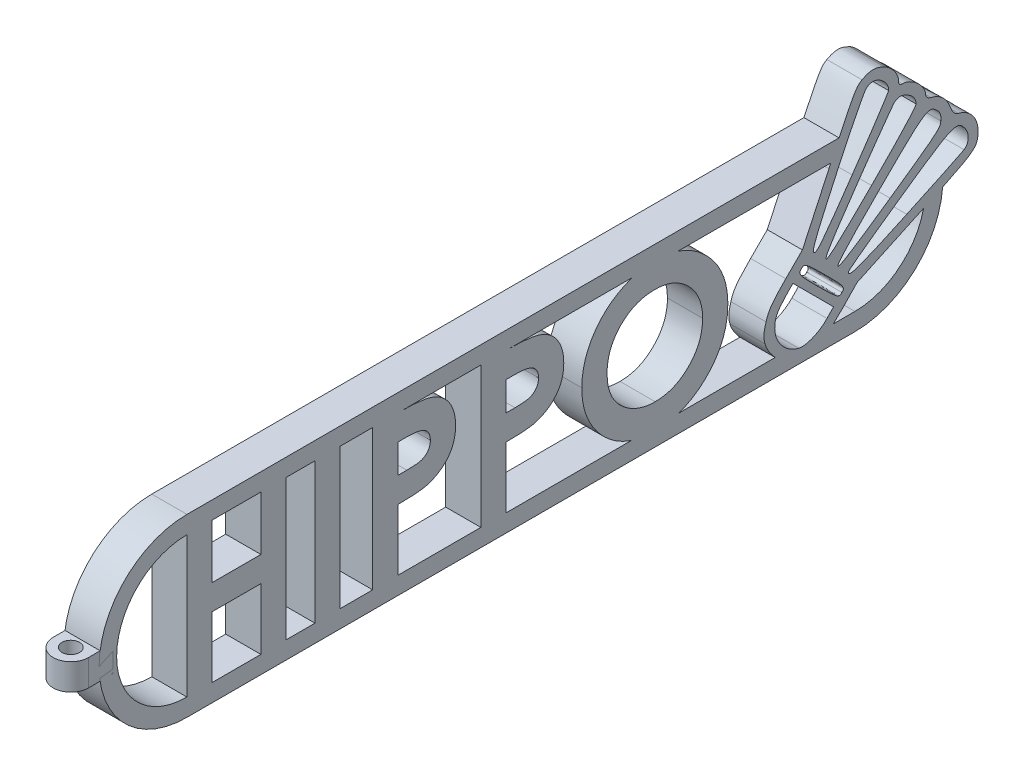
SolidWorks part; units mm, degrees
ref_plane "Front Plane" through (0, 0, 0) normal (0, 0, 1) x (1, 0, 0)
ref_plane "Top Plane" through (0, 0, 0) normal (0, 1, 0) x (1, 0, 0)
ref_plane "Right Plane" through (0, 0, 0) normal (1, 0, 0) x (0, 0, -1)
sketch "Sketch1" plane through (0, 0, 0) normal (1, 0, 0) x (0, 0, -1)
  text T0 "<b>HIPPO</b>" font "Century Gothic" height 16
extrude "Boss-Extrude1" add sketch "Sketch1" along normal blind 3
sketch "Sketch2" plane through (3, 0, 0) normal (1, 0, 0) x (0, 0, -1)
  line L0 (1.8462, 0) -> (1.8462, 16) construction
  line L1 (1.8462, -2) -> (84.1318, -2)
  line L2 (74.8872, 15.5422) -> (71.8699, 9.0451)
  line L3 (71.8699, 9.0451) -> (69.9759, 7.1511)
  line L4 (76.4068, 0.9844) -> (78.0807, 2.7243)
  line L5 (78.0807, 2.7243) -> (84.6438, 5.7856)
  line L6 (69.9979, 5.4772) -> (70.7907, 6.2921)
  line L7 (70.7907, 6.2921) -> (73.1032, 3.9796)
  line L8 (73.1032, 3.9796) -> (75.4158, 1.6671)
  line L9 (75.4158, 1.6671) -> (74.6669, 0.8963)
  line L10 (1.8462, 8) -> (77.8462, 8)
  line L11 (1.8462, 18) -> (77.8462, 18)
  line L12 (1.8462, 16) -> (77.8462, 16)
  line L13 (1.8462, 0) -> (77.8462, 0)
  circle A0 centre (1.8462, 8) radius 8
  circle A1 centre (1.8462, 8) radius 10
  circle A2 centre (77.8462, 8) radius 10
  circle A3 centre (77.8462, 8) radius 8
  spline S0 degree 3 poles (78.6533, 22.4136) (77.9705, 22.0833) (77.6402, 21.4446) (74.8872, 15.5422) knots 0 0 0 0 1 1 1 1
  spline S1 degree 3 poles (69.9759, 7.1511) (68.3681, 5.5213) (68.0377, 5.0588) (67.7294, 4.0237) knots 0 0 0 0 1 1 1 1
  spline S2 degree 3 poles (67.7294, 4.0237) (67.4431, 3.0326) (67.4211, 2.6141) (67.6193, 1.8873) knots 0 0 0 0 1 1 1 1
  spline S3 degree 3 poles (67.6193, 1.8873) (67.9056, 0.8082) (69.1389, -0.6234) (70.2842, -1.218) knots 0 0 0 0 1 1 1 1
  spline S4 degree 3 poles (70.2842, -1.218) (72.2003, -2.1871) (73.9842, -1.5264) (76.4068, 0.9844) knots 0 0 0 0 1 1 1 1
  spline S5 degree 3 poles (84.6438, 5.7856) (91.7795, 9.0671) (91.8456, 9.1332) (91.8456, 10.8511) knots 0 0 0 0 1 1 1 1
  spline S6 degree 3 poles (91.8456, 10.8511) (91.8456, 12.1505) (90.9206, 13.3178) (89.6212, 13.6261) knots 0 0 0 0 1 1 1 1
  spline S7 degree 3 poles (89.6212, 13.6261) (89.2027, 13.7362) (88.9384, 14.0225) (88.6742, 14.7713) knots 0 0 0 0 1 1 1 1
  spline S8 degree 3 poles (88.6742, 14.7713) (88.2777, 15.8065) (87.5069, 16.5112) (86.4938, 16.7535) knots 0 0 0 0 1 1 1 1
  spline S9 degree 3 poles (86.4938, 16.7535) (86.1414, 16.8416) (85.8991, 17.0618) (85.8991, 17.2821) knots 0 0 0 0 1 1 1 1
  spline S10 degree 3 poles (85.8991, 17.2821) (85.8991, 18.2952) (84.3575, 19.7267) (83.2563, 19.7267) knots 0 0 0 0 1 1 1 1
  spline S11 degree 3 poles (83.2563, 19.7267) (82.9479, 19.7267) (82.8158, 19.8589) (82.8158, 20.1892) knots 0 0 0 0 1 1 1 1
  spline S12 degree 3 poles (82.8158, 20.1892) (82.8158, 20.938) (82.089, 21.9511) (81.2301, 22.3916) knots 0 0 0 0 1 1 1 1
  spline S13 degree 3 poles (81.2301, 22.3916) (80.217, 22.9202) (79.6223, 22.9202) (78.6533, 22.4136) knots 0 0 0 0 1 1 1 1
  spline S14 degree 3 poles (81.2301, 20.894) (81.5384, 20.5416) (81.7146, 20.1231) (81.6706, 19.8589) knots 0 0 0 0 1 1 1 1
  spline S15 degree 3 poles (81.6706, 19.8589) (81.6045, 19.5946) (79.7545, 16.7975) (77.5301, 13.6041) knots 0 0 0 0 1 1 1 1
  spline S16 degree 3 poles (77.5301, 13.6041) (74.0723, 8.6267) (73.4556, 7.8558) (73.1913, 8.1201) knots 0 0 0 0 1 1 1 1
  spline S17 degree 3 poles (73.1913, 8.1201) (72.9271, 8.3844) (73.2794, 9.3094) (75.7681, 14.6832) knots 0 0 0 0 1 1 1 1
  spline S18 degree 3 poles (75.7681, 14.6832) (77.3539, 18.119) (78.8735, 21.1142) (79.1378, 21.3345) knots 0 0 0 0 1 1 1 1
  spline S19 degree 3 poles (79.1378, 21.3345) (79.7324, 21.841) (80.5473, 21.6648) (81.2301, 20.894) knots 0 0 0 0 1 1 1 1
  spline S20 degree 3 poles (83.7628, 18.3612) (84.4015, 18.0309) (84.7759, 17.5243) (84.7979, 16.9737) knots 0 0 0 0 1 1 1 1
  spline S21 degree 3 poles (84.7979, 16.9737) (84.7979, 16.6874) (83.036, 14.7713) (79.7324, 11.4677) knots 0 0 0 0 1 1 1 1
  spline S22 degree 3 poles (79.7324, 11.4677) (73.2134, 4.9707) (72.9931, 5.1249) (78.2128, 12.613) knots 0 0 0 0 1 1 1 1
  spline S23 degree 3 poles (78.2128, 12.613) (80.3051, 15.6082) (82.1551, 18.2071) (82.3533, 18.3612) knots 0 0 0 0 1 1 1 1
  spline S24 degree 3 poles (82.3533, 18.3612) (82.7717, 18.6916) (83.1462, 18.6916) (83.7628, 18.3612) knots 0 0 0 0 1 1 1 1
  spline S25 degree 3 poles (87.2426, 15.0797) (87.5509, 14.7713) (87.6611, 14.419) (87.617, 13.8904) knots 0 0 0 0 1 1 1 1
  spline S26 degree 3 poles (87.617, 13.8904) (87.5509, 13.1856) (87.2206, 12.9213) (81.8467, 9.1552) knots 0 0 0 0 1 1 1 1
  spline S27 degree 3 poles (81.8467, 9.1552) (77.7943, 6.3142) (76.0765, 5.235) (75.9003, 5.4112) knots 0 0 0 0 1 1 1 1
  spline S28 degree 3 poles (75.9003, 5.4112) (75.7461, 5.5653) (77.0896, 7.063) (80.6134, 10.5868) knots 0 0 0 0 1 1 1 1
  spline S29 degree 3 poles (80.6134, 10.5868) (85.9212, 15.8946) (86.2295, 16.0928) (87.2426, 15.0797) knots 0 0 0 0 1 1 1 1
  spline S30 degree 3 poles (90.2819, 11.8862) (90.8986, 11.0933) (90.8766, 10.1463) (90.2599, 9.7279) knots 0 0 0 0 1 1 1 1
  spline S31 degree 3 poles (90.2599, 9.7279) (89.9736, 9.5517) (87.0444, 8.1421) (83.7408, 6.6225) knots 0 0 0 0 1 1 1 1
  spline S32 degree 3 poles (83.7408, 6.6225) (78.3009, 4.0897) (76.8914, 3.6052) (77.1336, 4.31) knots 0 0 0 0 1 1 1 1
  spline S33 degree 3 poles (77.1336, 4.31) (77.1777, 4.4421) (79.7324, 6.3142) (82.8158, 8.4725) knots 0 0 0 0 1 1 1 1
  spline S34 degree 3 poles (82.8158, 8.4725) (88.9384, 12.7672) (89.423, 12.9874) (90.2819, 11.8862) knots 0 0 0 0 1 1 1 1
  spline S35 degree 3 poles (76.3628, 2.6141) (76.0104, 2.2397) (75.8783, 2.3498) (73.6759, 4.5302) knots 0 0 0 0 1 1 1 1
  spline S36 degree 3 poles (73.6759, 4.5302) (71.4955, 6.7106) (71.3854, 6.8427) (71.7378, 7.2392) knots 0 0 0 0 1 1 1 1
  spline S37 degree 3 poles (71.7378, 7.2392) (72.0901, 7.6136) (72.2003, 7.5255) (74.4247, 5.3231) knots 0 0 0 0 1 1 1 1
  spline S38 degree 3 poles (74.4247, 5.3231) (76.6271, 3.1207) (76.7372, 2.9665) (76.3628, 2.6141) knots 0 0 0 0 1 1 1 1
  spline S39 degree 3 poles (74.6669, 0.8963) (73.764, -0.0508) (72.2884, -0.6454) (71.4294, -0.4252) knots 0 0 0 0 1 1 1 1
  spline S40 degree 3 poles (71.4294, -0.4252) (69.9318, -0.0728) (68.7205, 1.4248) (68.7205, 2.8784) knots 0 0 0 0 1 1 1 1
  spline S41 degree 3 poles (68.7205, 2.8784) (68.7205, 3.8695) (68.9848, 4.3981) (69.9979, 5.4772) knots 0 0 0 0 1 1 1 1
  point P69 (0, 0)
  line M5 (1.8462, 0) -> (4.7179, 0)
  line M9 (10.2564, 0) -> (13.1282, 0)
  line M11 (13.1282, 16) -> (10.2564, 16)
  line M15 (4.7179, 16) -> (1.8462, 16)
  dimension "D2" = 2
  dimension "D1" = 2
extrude "Boss-Extrude2" add sketch "Sketch2" against normal blind 3 contours A2 S34 S30 S31 S5 S6 S7 S8 S9 S10 S11 S12 S13 S0 L11 S18 S19 S14 S15 S23 S24 S20 S21 S29 S25 S26 | A3 S23 A2 S15 | L12 S18 A2 S0 | A3 S18 L12 S0 L2 | S22 S23 A3 S15 S16 S17 S18 L2 L3 L10 | A2 S18 L11 S0 | A3 S29 A2 S21 | L9 S39 A3 S4 L4 L5 S5 S31 S32 S33 S34 S26 S27 S28 S29 S21 S22 L10 L3 S1 L6 L7 L8 S37 S38 S35 S36 | A3 S34 A2 S26 | A2 S31 A3 S5 | S5 A3 L13 S4 A2 | L13 S39 A2 S4 | A3 S39 L13 S4 | S39 S40 L13 S3 S4 A2 | S40 S41 A2 S1 S2 S3 L13 | A2 S41 L6 A3 S1 | S0 A2 L12 | S0 L11 A1 L12 A2 M11 | S4 S3 L13 A1 L1 A2 M9 | L12 A1 L13 A0 M5 M15 region at (3, -1.033, -38.6325) region at (3, 8, 7.8977) region at (3, -1.6179, -75.8061) region at (3, 17.0225, -39.8175) region at (3, -0.8404, -71.2672) region at (3, -0.4458, -73.8685) region at (3, 7.4077, -86.8029) region at (3, 16.1247, -84.8789) region at (3, 17.9452, -76.4366) region at (3, 0.2603, -74.6585) region at (3, 6.211, -85.0591) region at (3, 16.6879, -74.2086) region at (3, 16.9636, -76.2066) region at (3, 2.153, -68.4649) region at (3, 15.8059, -75.5124) region at (3, 5.4531, -69.219) region at (3, 11.4875, -86.1504) region at (3, 16.6454, -80.3292) region at (3, 8.4352, -71.4347) region at (3, 14.7142, -83.8581)
ref_plane "Plane1" through (0, 8, 0) normal (0, -1, 0) x (-1, 0, 0)
sketch "Sketch4" plane through (3, 0, 0) normal (1, 0, 0) x (0, 0, -1)
  line L1 (1.8462, 0) -> (1.8462, 16)
  line L2 (1.8462, 0) -> (1.8462, 16)
  line L4 (1.8462, -2) -> (77.8462, -2)
  line L5 (75.3816, 0) -> (77.8462, 0)
  line L6 (78.0807, 2.7243) -> (76.4068, 0.9844)
  line L7 (84.6438, 5.7856) -> (78.0807, 2.7243)
  line L8 (75.3816, 0) -> (77.8462, 0)
  line L9 (78.0807, 2.7243) -> (76.4068, 0.9844)
  line L10 (84.6438, 5.7856) -> (78.0807, 2.7243)
  line L11 (70.7907, 6.2921) -> (69.9979, 5.4772)
  line L12 (75.4158, 1.6671) -> (70.7907, 6.2921)
  line L13 (74.6669, 0.8963) -> (75.4158, 1.6671)
  line L14 (70.7907, 6.2921) -> (69.9979, 5.4772)
  line L15 (75.4158, 1.6671) -> (70.7907, 6.2921)
  line L16 (74.6669, 0.8963) -> (75.4158, 1.6671)
  line L17 (25.8462, 9.8462) -> (26.8622, 9.8462)
  line L18 (10.2564, 0) -> (10.2564, 6.9744)
  line L19 (4.7179, 0) -> (10.2564, 0)
  line L20 (4.7179, 6.9744) -> (4.7179, 0)
  line L21 (10.2564, 6.9744) -> (4.7179, 6.9744)
  line L22 (10.2564, 0) -> (10.2564, 6.9744)
  line L23 (4.7179, 0) -> (10.2564, 0)
  line L24 (4.7179, 6.9744) -> (4.7179, 0)
  line L25 (10.2564, 6.9744) -> (4.7179, 6.9744)
  line L26 (4.7179, 16) -> (4.7179, 9.8462)
  line L27 (10.2564, 16) -> (4.7179, 16)
  line L28 (10.2564, 9.8462) -> (10.2564, 16)
  line L29 (4.7179, 9.8462) -> (10.2564, 9.8462)
  line L30 (4.7179, 16) -> (4.7179, 9.8462)
  line L31 (10.2564, 16) -> (4.7179, 16)
  line L32 (10.2564, 9.8462) -> (10.2564, 16)
  line L33 (4.7179, 9.8462) -> (10.2564, 9.8462)
  line L34 (13.1282, 16) -> (13.1282, 0)
  line L35 (16.4103, 16) -> (13.1282, 16)
  line L36 (16.4103, 0) -> (16.4103, 16)
  line L37 (13.1282, 0) -> (16.4103, 0)
  line L38 (13.1282, 16) -> (13.1282, 0)
  line L39 (16.4103, 16) -> (13.1282, 16)
  line L40 (16.4103, 0) -> (16.4103, 16)
  line L41 (13.1282, 0) -> (16.4103, 0)
  line L42 (19.2821, 16) -> (19.2821, 0)
  line L43 (22.9744, 16) -> (19.2821, 16)
  line L44 (22.9744, 0) -> (22.9744, 16)
  line L45 (19.2821, 0) -> (22.9744, 0)
  line L46 (19.2821, 16) -> (19.2821, 0)
  line L47 (22.9744, 16) -> (19.2821, 16)
  line L48 (22.9744, 0) -> (22.9744, 16)
  line L49 (19.2821, 0) -> (22.9744, 0)
  line L50 (25.8462, 13.1282) -> (25.8462, 9.8462)
  line L51 (26.75, 13.1282) -> (25.8462, 13.1282)
  line L52 (25.8462, 9.8462) -> (26.8622, 9.8462)
  line L53 (25.8462, 13.1282) -> (25.8462, 9.8462)
  line L54 (26.75, 13.1282) -> (25.8462, 13.1282)
  line L55 (38.1538, 9.8462) -> (39.1699, 9.8462)
  line L56 (35.2821, 16) -> (26.1795, 16)
  line L57 (35.2821, 0) -> (35.2821, 16)
  line L58 (25.8462, 0) -> (35.2821, 0)
  line L59 (25.8462, 6.9744) -> (25.8462, 0)
  line L60 (35.2821, 16) -> (26.1795, 16)
  line L61 (35.2821, 0) -> (35.2821, 16)
  line L62 (25.8462, 0) -> (35.2821, 0)
  line L63 (25.8462, 6.9744) -> (25.8462, 0)
  line L64 (38.1538, 13.1282) -> (38.1538, 9.8462)
  line L65 (39.0577, 13.1282) -> (38.1538, 13.1282)
  line L66 (38.1538, 9.8462) -> (39.1699, 9.8462)
  line L67 (38.1538, 13.1282) -> (38.1538, 9.8462)
  line L68 (39.0577, 13.1282) -> (38.1538, 13.1282)
  line L69 (38.1538, 0) -> (52.4084, 0)
  line L70 (57.788, 0) -> (68.765, 0)
  line L71 (75.1008, 16) -> (57.7211, 16)
  line L72 (71.8699, 9.0451) -> (74.8872, 15.5422)
  line L73 (69.9759, 7.1511) -> (71.8699, 9.0451)
  line L74 (57.788, 0) -> (68.765, 0)
  line L75 (75.1008, 16) -> (57.7211, 16)
  line L76 (71.8699, 9.0451) -> (74.8872, 15.5422)
  line L77 (69.9759, 7.1511) -> (71.8699, 9.0451)
  line L78 (38.1538, 6.9744) -> (38.1538, 0)
  line L79 (52.5121, 16) -> (38.4872, 16)
  line L80 (38.1538, 0) -> (52.4084, 0)
  line L81 (38.1538, 6.9744) -> (38.1538, 0)
  line L82 (52.5121, 16) -> (38.4872, 16)
  line L83 (76.038, 18) -> (1.8462, 18)
  line L84 (1.8462, -2) -> (77.8462, -2)
  line L85 (76.038, 18) -> (1.8462, 18)
  arc A1 (1.8462, 16) -> (1.8462, 0) centre (1.8462, 8) ccw
  arc A2 (1.8462, 16) -> (1.8462, 0) centre (1.8462, 8) ccw
  arc A3 (77.8462, 0) -> (85.6524, 6.2499) centre (77.8462, 8) ccw
  arc A4 (77.8462, 0) -> (85.6524, 6.2499) centre (77.8462, 8) ccw
  arc A5 (75.1008, 16) -> (74.8872, 15.5422) centre (1612.4659, -701.5915) ccw
  arc A6 (75.1008, 16) -> (74.8872, 15.5422) centre (1612.4659, -701.5915) ccw
  arc A8 (1.8462, 18) -> (1.8462, -2) centre (1.8462, 8) ccw
  arc A9 (77.8462, -2) -> (87.8186, 7.2582) centre (77.8462, 8) ccw
  arc A10 (1.8462, 18) -> (1.8462, -2) centre (1.8462, 8) ccw
  arc A11 (77.8462, -2) -> (87.8186, 7.2582) centre (77.8462, 8) ccw
  spline S2 degree 3 poles (3398.8035, 2205.2477) (-3328.0157, -1472.5897) (3668.6024, 610.8811) (-3872.9047, 380.9278) knots -14.449432 -14.449432 -14.449432 -14.449432 18.771452 18.771452 18.771452 18.771452 only from (76.4068, 0.9844) to (75.3816, 0)
  spline S3 degree 3 poles (3203.2755, 2509.8402) (-3117.551, -2311.6664) (3402.2738, 2198.6029) (-3322.7745, -2087.971) knots -8.590322 -8.590322 -8.590322 -8.590322 6.910663 6.910663 6.910663 6.910663 only from (85.6524, 6.2499) to (84.6438, 5.7856)
  spline S4 degree 3 poles (76.4068, 0.9844) (76.0522, 0.6168) (75.7112, 0.2889) (75.3816, 0) knots 0.853614 0.853614 0.853614 0.853614 1 1 1 1
  spline S5 degree 3 poles (85.6524, 6.2499) (85.3329, 6.1026) (84.997, 5.948) (84.6438, 5.7856) knots 0 0 0 0 0.049503 0.049503 0.049503 0.049503
  spline S7 degree 3 poles (3662.2888, 1757.5012) (-3665.795, -1581.4606) (3896.598, 1366.2039) (-3765.3568, -1110.8259) knots -14.001225 -14.001225 -14.001225 -14.001225 15.36382 15.36382 15.36382 15.36382 only from (71.4294, -0.4252) to (74.6669, 0.8963)
  spline S8 degree 3 poles (3245.6319, -2431.8344) (-3158.4345, 2357.2343) (3374.3152, -2236.2437) (-3319.5499, 2126.5847) knots -10.133548 -10.133548 -10.133548 -10.133548 12.175041 12.175041 12.175041 12.175041 only from (74.4247, 5.3231) to (71.7378, 7.2392)
  spline S9 degree 3 poles (1083.5594, 3850.6057) (607.2877, -1937.4836) (-1991.6838, 100.7189) (3666.0332, 1714.9301) knots -11.026375 -11.026375 -11.026375 -11.026375 11.921239 11.921239 11.921239 11.921239 only from (78.2128, 12.613) to (79.7324, 11.4677)
  spline S10 degree 3 poles (1641.4402, 3695.284) (-1451.7816, -3694.7067) (1537.8192, 3732.2131) (-1312.2249, -3743.7308) knots -8.732068 -8.732068 -8.732068 -8.732068 11.138373 11.138373 11.138373 11.138373 only from (75.7681, 14.6832) to (73.1913, 8.1201)
  spline S11 degree 3 poles (-1691.1806, -3565.3513) (1950.1636, 3740.9223) (-1835.9314, -3700.9685) (1948.2953, 3549.0256) knots -10.471686 -10.471686 -10.471686 -10.471686 12.804548 12.804548 12.804548 12.804548 only from (79.1378, 21.3345) to (75.7681, 14.6832)
  spline S12 degree 3 poles (-3902.9668, 52.302) (3987.908, -662.1434) (-3687.842, 1284.6522) (3652.9871, -1753.1124) knots -22.160522 -22.160522 -22.160522 -22.160522 22.114231 22.114231 22.114231 22.114231 only from (81.2301, 20.894) to (79.1378, 21.3345)
  spline S13 degree 3 poles (-1660.4023, 3619.2004) (1672.625, -3686.2371) (-1329.5129, 3799.7603) (1281.2887, -3793.0689) knots -24.742089 -24.742089 -24.742089 -24.742089 26.636419 26.636419 26.636419 26.636419 only from (81.6706, 19.8589) to (81.2301, 20.894)
  spline S14 degree 3 poles (2243.6041, 3376.228) (-2219.7676, -3488.6997) (2391.2134, 3493.9099) (-2149.5274, -3299.8374) knots -11.951522 -11.951522 -11.951522 -11.951522 11.519907 11.519907 11.519907 11.519907 only from (77.5301, 13.6041) to (81.6706, 19.8589)
  spline S15 degree 3 poles (-2493.0411, -3059.458) (2574.1796, 3146.3373) (-2373.0325, -3175.9895) (2473.7465, 3216.155) knots -10.235719 -10.235719 -10.235719 -10.235719 9.730338 9.730338 9.730338 9.730338 only from (73.1913, 8.1201) to (77.5301, 13.6041)
  spline S16 degree 3 poles (75.7681, 14.6832) (73.2794, 9.3094) (72.9271, 8.3844) (73.1913, 8.1201) knots 0 0 0 0 1 1 1 1
  spline S17 degree 3 poles (79.1378, 21.3345) (78.8735, 21.1142) (77.3539, 18.119) (75.7681, 14.6832) knots 0 0 0 0 1 1 1 1
  spline S18 degree 3 poles (81.2301, 20.894) (80.5473, 21.6648) (79.7324, 21.841) (79.1378, 21.3345) knots 0 0 0 0 1 1 1 1
  spline S19 degree 3 poles (81.6706, 19.8589) (81.7146, 20.1231) (81.5384, 20.5416) (81.2301, 20.894) knots 0 0 0 0 1 1 1 1
  spline S20 degree 3 poles (77.5301, 13.6041) (79.7545, 16.7975) (81.6045, 19.5946) (81.6706, 19.8589) knots 0 0 0 0 1 1 1 1
  spline S21 degree 3 poles (73.1913, 8.1201) (73.4556, 7.8558) (74.0723, 8.6267) (77.5301, 13.6041) knots 0 0 0 0 1 1 1 1
  spline S22 degree 3 poles (-2176.0719, -3282.7953) (2439.0711, 3449.1497) (-2293.0545, -3426.5564) (2353.9475, 3301.8808) knots -10.65011 -10.65011 -10.65011 -10.65011 13.034154 13.034154 13.034154 13.034154 only from (82.3533, 18.3612) to (78.2128, 12.613)
  spline S23 degree 3 poles (4041.3379, -533.1759) (-3834.4966, 213.1099) (3997.2825, 202.3854) (-3869.2711, -565.3494) knots -23.09562 -23.09562 -23.09562 -23.09562 24.773781 24.773781 24.773781 24.773781 only from (83.7628, 18.3612) to (82.3533, 18.3612)
  spline S24 degree 3 poles (-2738.2129, 2838.4609) (2525.552, -3137.8393) (-1904.1707, 3471.2601) (1544.442, -3691.9755) knots -28.231758 -28.231758 -28.231758 -28.231758 30.196206 30.196206 30.196206 30.196206 only from (84.7979, 16.9737) to (83.7628, 18.3612)
  spline S25 degree 3 poles (2219.6275, 3340.4099) (-3988.2905, -4500.1893) (3827.8531, 3873.0493) (-2752.2579, -2802.2224) knots -31.935784 -31.935784 -31.935784 -31.935784 18.597569 18.597569 18.597569 18.597569 only from (79.7324, 11.4677) to (84.7979, 16.9737)
  spline S26 degree 3 poles (78.2128, 12.613) (72.9931, 5.1249) (73.2134, 4.9707) (79.7324, 11.4677) knots 0 0 0 0 1 1 1 1
  spline S27 degree 3 poles (82.3533, 18.3612) (82.1551, 18.2071) (80.3051, 15.6082) (78.2128, 12.613) knots 0 0 0 0 1 1 1 1
  spline S28 degree 3 poles (83.7628, 18.3612) (83.1462, 18.6916) (82.7717, 18.6916) (82.3533, 18.3612) knots 0 0 0 0 1 1 1 1
  spline S29 degree 3 poles (84.7979, 16.9737) (84.7759, 17.5243) (84.4015, 18.0309) (83.7628, 18.3612) knots 0 0 0 0 1 1 1 1
  spline S30 degree 3 poles (79.7324, 11.4677) (83.036, 14.7713) (84.7979, 16.6874) (84.7979, 16.9737) knots 0 0 0 0 1 1 1 1
  spline S31 degree 3 poles (-3066.9036, -2457.2821) (3189.1374, 2517.7206) (-2963.5188, -2546.6324) (3090.9577, 2654.8825) knots -7.650295 -7.650295 -7.650295 -7.650295 9.619482 9.619482 9.619482 9.619482 only from (81.8467, 9.1552) to (87.617, 13.8904)
  spline S32 degree 3 poles (-3420.4834, -1932.3599) (3708.7133, 2282.0815) (-3460.812, -2345.5677) (3380.3356, 2271.2505) knots -18.576445 -18.576445 -18.576445 -18.576445 14.352502 14.352502 14.352502 14.352502 only from (75.9003, 5.4112) to (81.8467, 9.1552)
  spline S33 degree 3 poles (2949.1906, 2798.1479) (-2957.8136, -2975.5538) (3103.5037, 3054.5658) (-2663.5684, -2908.2041) knots -13.235152 -13.235152 -13.235152 -13.235152 19.430166 19.430166 19.430166 19.430166 only from (80.6134, 10.5868) to (75.9003, 5.4112)
  spline S34 degree 3 poles (3560.9209, 1993.6135) (-3246.9405, -2160.7019) (3316.2473, 2353.498) (-3070.6661, -2451.6) knots -8.33373 -8.33373 -8.33373 -8.33373 8.314581 8.314581 8.314581 8.314581 only from (87.2426, 15.0797) to (80.6134, 10.5868)
  spline S35 degree 3 poles (818.7962, -3914.4503) (-968.034, 3784.8593) (1496.8532, -3635.1385) (-1706.2685, 3584.7352) knots -29.576927 -29.576927 -29.576927 -29.576927 31.263424 31.263424 31.263424 31.263424 only from (87.617, 13.8904) to (87.2426, 15.0797)
  spline S36 degree 3 poles (81.8467, 9.1552) (87.2206, 12.9213) (87.5509, 13.1856) (87.617, 13.8904) knots 0 0 0 0 1 1 1 1
  spline S37 degree 3 poles (75.9003, 5.4112) (76.0765, 5.235) (77.7943, 6.3142) (81.8467, 9.1552) knots 0 0 0 0 1 1 1 1
  spline S38 degree 3 poles (80.6134, 10.5868) (77.0896, 7.063) (75.7461, 5.5653) (75.9003, 5.4112) knots 0 0 0 0 1 1 1 1
  spline S39 degree 3 poles (87.2426, 15.0797) (86.2295, 16.0928) (85.9212, 15.8946) (80.6134, 10.5868) knots 0 0 0 0 1 1 1 1
  spline S40 degree 3 poles (87.617, 13.8904) (87.6611, 14.419) (87.5509, 14.7713) (87.2426, 15.0797) knots 0 0 0 0 1 1 1 1
  spline S41 degree 3 poles (3653.7082, 1810.546) (-3652.9096, -1852.2843) (3822.3539, 1845.7708) (-3504.7072, -1743.7789) knots -11.926091 -11.926091 -11.926091 -11.926091 11.61226 11.61226 11.61226 11.61226 only from (83.7408, 6.6225) to (90.2599, 9.7279)
  spline S42 degree 3 poles (-3769.4158, -1084.4312) (3943.5137, 1339.5694) (-3734.9681, -1469.0708) (3780.149, 1534.2354) knots -12.484067 -12.484067 -12.484067 -12.484067 10.943657 10.943657 10.943657 10.943657 only from (77.1336, 4.31) to (83.7408, 6.6225)
  spline S43 degree 3 poles (-3119.3021, -2388.2991) (3453.2703, 2492.5539) (-3293.1517, -2451.1802) (3320.394, 2345.0708) knots -12.142018 -12.142018 -12.142018 -12.142018 11.645217 11.645217 11.645217 11.645217 only from (82.8158, 8.4725) to (77.1336, 4.31)
  spline S44 degree 3 poles (3848.8812, 1373.4178) (-3562.3293, -1567.477) (3667.0055, 1769.2314) (-3440.104, -1884.3095) knots -8.472057 -8.472057 -8.472057 -8.472057 8.419331 8.419331 8.419331 8.419331 only from (90.2819, 11.8862) to (82.8158, 8.4725)
  spline S45 degree 3 poles (-247.3283, 3990.3134) (41.0963, -3999.1804) (545.8079, 3993.3576) (-788.1207, -3883.4417) knots -17.288999 -17.288999 -17.288999 -17.288999 18.710016 18.710016 18.710016 18.710016 only from (90.2599, 9.7279) to (90.2819, 11.8862)
  spline S46 degree 3 poles (83.7408, 6.6225) (87.0444, 8.1421) (89.9736, 9.5517) (90.2599, 9.7279) knots 0 0 0 0 1 1 1 1
  spline S47 degree 3 poles (77.1336, 4.31) (76.8914, 3.6052) (78.3009, 4.0897) (83.7408, 6.6225) knots 0 0 0 0 1 1 1 1
  spline S48 degree 3 poles (82.8158, 8.4725) (79.7324, 6.3142) (77.1777, 4.4421) (77.1336, 4.31) knots 0 0 0 0 1 1 1 1
  spline S49 degree 3 poles (90.2819, 11.8862) (89.423, 12.9874) (88.9384, 12.7672) (82.8158, 8.4725) knots 0 0 0 0 1 1 1 1
  spline S50 degree 3 poles (90.2599, 9.7279) (90.8766, 10.1463) (90.8986, 11.0933) (90.2819, 11.8862) knots 0 0 0 0 1 1 1 1
  spline S51 degree 3 poles (2226.2291, -3369.2735) (-2199.2504, 3283.3199) (2458.9196, -3203.9324) (-2394.7214, 3151.668) knots -11.348512 -11.348512 -11.348512 -11.348512 11.266484 11.266484 11.266484 11.266484 only from (76.3628, 2.6141) to (74.4247, 5.3231)
  spline S52 degree 3 poles (-3108.0054, 2427.9194) (3318.4109, -2330.2254) (-3239.8458, 2224.9499) (3483.4831, -2090.8877) knots -10.243964 -10.243964 -10.243964 -10.243964 12.306567 12.306567 12.306567 12.306567 only from (73.6759, 4.5302) to (76.3628, 2.6141)
  spline S53 degree 3 poles (-2027.9667, 3410.5578) (2298.8876, -3302.9973) (-2266.395, 3242.6264) (2504.5121, -3171.3971) knots -11.246626 -11.246626 -11.246626 -11.246626 11.218548 11.218548 11.218548 11.218548 only from (71.7378, 7.2392) to (73.6759, 4.5302)
  spline S54 degree 3 poles (74.4247, 5.3231) (72.2003, 7.5255) (72.0901, 7.6136) (71.7378, 7.2392) knots 0 0 0 0 1 1 1 1
  spline S55 degree 3 poles (76.3628, 2.6141) (76.7372, 2.9665) (76.6271, 3.1207) (74.4247, 5.3231) knots 0 0 0 0 1 1 1 1
  spline S56 degree 3 poles (73.6759, 4.5302) (75.8783, 2.3498) (76.0104, 2.2397) (76.3628, 2.6141) knots 0 0 0 0 1 1 1 1
  spline S57 degree 3 poles (71.7378, 7.2392) (71.3854, 6.8427) (71.4955, 6.7106) (73.6759, 4.5302) knots 0 0 0 0 1 1 1 1
  spline S58 degree 3 poles (2920.3551, -2795.4819) (-2554.5373, 3081.8895) (2411.2536, -3299.6806) (-1934.0115, 3454.9016) knots -13.355319 -13.355319 -13.355319 -13.355319 14.387707 14.387707 14.387707 14.387707 only from (68.7205, 2.8784) to (71.4294, -0.4252)
  spline S59 degree 3 poles (2056.7145, 3475.7087) (-1724.927, -3505.3927) (1679.2284, 3599.0436) (-1369.3069, -3727.8202) knots -14.481772 -14.481772 -14.481772 -14.481772 15.937559 15.937559 15.937559 15.937559 only from (69.9979, 5.4772) to (68.7205, 2.8784)
  spline S60 degree 3 poles (71.4294, -0.4252) (72.2884, -0.6454) (73.764, -0.0508) (74.6669, 0.8963) knots 0 0 0 0 1 1 1 1
  spline S61 degree 3 poles (68.7205, 2.8784) (68.7205, 1.4248) (69.9318, -0.0728) (71.4294, -0.4252) knots 0 0 0 0 1 1 1 1
  spline S62 degree 3 poles (69.9979, 5.4772) (68.9848, 4.3981) (68.7205, 3.8695) (68.7205, 2.8784) knots 0 0 0 0 1 1 1 1
  spline S63 degree 3 poles (1654.4282, 3667.4926) (23.5895, -27.9887) (34.1837, 10.9726) (28.4438, 12.9542) (28.2324, 13.0075) (27.9915, 13.0518) (27.7218, 13.0862) (27.4235, 13.1124) (8.673, 13.7177) (-10.0794, -12.057) (-13.112, 4012.472) knots -8.463627 -8.463627 -8.463627 -8.463627 0.082101 0.173825 0.278953 0.396639 0.527316 0.671298 0.828754 27.604848 27.604848 27.604848 27.604848 only from (28.7853, 12.8109) to (26.75, 13.1282)
  spline S64 degree 3 poles (4016.0561, 337.084) (-13.681, -5.9368) (30.6901, 4.9208) (29.495, 11.8885) (29.4377, 12.0841) (29.3546, 12.2635) (29.2471, 12.4263) (29.1161, 12.5724) (24.4224, 16.6446) (-8.0727, -19.3212) (2299.6561, 3305.3954) knots -12.573831 -12.573831 -12.573831 -12.573831 0.137788 0.267341 0.390444 0.511778 0.629509 0.747829 0.871885 12.00493 12.00493 12.00493 12.00493 only from (29.5385, 11.4583) to (28.7853, 12.8109)
  spline S65 degree 3 poles (82.6352, -3989.4601) (-6.2739, 55.6737) (11.3504, 8.7728) (27.8518, 9.8807) (28.2252, 9.9283) (28.5201, 9.9966) (28.753, 10.1003) (28.9538, 10.2203) (29.1261, 10.3719) (29.2753, 10.5452) (29.3945, 10.7444) (29.4772, 10.9661) (31.0003, 17.7613) (-21.0415, 30.2799) (4007.9526, -399.2926) knots -13.479945 -13.479945 -13.479945 -13.479945 0.15516 0.285496 0.390503 0.470975 0.538446 0.603655 0.666587 0.730199 0.794945 0.860228 0.928121 6.609006 6.609006 6.609006 6.609006 only from (26.8622, 9.8462) to (29.5385, 11.4583)
  spline S66 degree 3 poles (28.7853, 12.8109) (28.7345, 12.8366) (28.6269, 12.891) (28.4438, 12.9542) (28.2324, 13.0075) (27.9915, 13.0518) (27.7218, 13.0862) (27.4235, 13.1124) (27.0962, 13.123) (26.8686, 13.1264) (26.75, 13.1282) knots 0 0 0 0 0.082101 0.173825 0.278953 0.396639 0.527316 0.671298 0.828754 1 1 1 1
  spline S67 degree 3 poles (29.5385, 11.4583) (29.5359, 11.5333) (29.531, 11.6787) (29.495, 11.8885) (29.4377, 12.0841) (29.3546, 12.2635) (29.2471, 12.4263) (29.1161, 12.5724) (28.9632, 12.705) (28.8452, 12.7752) (28.7853, 12.8109) knots 0 0 0 0 0.137788 0.267341 0.390444 0.511778 0.629509 0.747829 0.871885 1 1 1 1
  spline S68 degree 3 poles (26.8622, 9.8462) (27.0471, 9.8473) (27.3872, 9.8495) (27.8518, 9.8807) (28.2252, 9.9283) (28.5201, 9.9966) (28.753, 10.1003) (28.9538, 10.2203) (29.1261, 10.3719) (29.2753, 10.5452) (29.3945, 10.7444) (29.4772, 10.9661) (29.5309, 11.2058) (29.5359, 11.3726) (29.5385, 11.4583) knots 0 0 0 0 0.15516 0.285496 0.390503 0.470975 0.538446 0.603655 0.666587 0.730199 0.794945 0.860228 0.928121 1 1 1 1
  spline S69 degree 3 poles (18.4847, 4015.3868) (-17.5505, -22.4135) (5.1105, 16.8134) (27.3755, 15.9753) (27.913, 15.936) (28.4053, 15.8875) (28.8521, 15.8194) (29.254, 15.7413) (29.6111, 15.6462) (29.9274, 15.5333) (30.2113, 15.4002) (30.4799, 15.2585) (30.7273, 15.0893) (30.9658, 14.911) (31.1818, 14.7064) (31.3889, 14.4892) (31.5782, 14.2508) (31.7506, 13.994) (31.9071, 13.7236) (32.0437, 13.4392) (32.1546, 13.1402) (32.2476, 12.8286) (32.3223, 12.5045) (32.372, 12.1657) (33.4736, 0.718) (-10.6404, -12.802) (4028.728, 171.1984) knots -7.331892 -7.331892 -7.331892 -7.331892 0.070781 0.136552 0.197012 0.252923 0.303687 0.349719 0.39124 0.428479 0.463057 0.49715 0.531002 0.564226 0.597701 0.631421 0.665597 0.700451 0.735881 0.771092 0.806975 0.843534 0.88094 0.919294 0.95918 4.764652 4.764652 4.764652 4.764652 only from (26.1795, 16) to (32.4103, 11.4551)
  spline S70 degree 3 poles (865.0881, -3903.9323) (38.1814, 49.2581) (37.5026, 8.4748) (28.552, 7.1085) (28.2132, 7.0672) (27.8285, 7.0317) (27.3976, 7.0076) (26.9211, 6.9888) (4.1279, 6.3916) (-18.9183, 40.8656) (6.0459, -3992.438) knots -8.01137 -8.01137 -8.01137 -8.01137 0.077373 0.167614 0.272108 0.390016 0.521363 0.667272 0.82681 21.401594 21.401594 21.401594 21.401594 only from (29.1058, 7.2179) to (25.8462, 6.9744)
  spline S71 degree 3 poles (4029.0232, -146.2279) (-13.6725, 36.5479) (33.6527, 22.504) (32.3618, 10.6739) (32.29, 10.3068) (32.1962, 9.9546) (32.0654, 9.623) (31.916, 9.3042) (31.7322, 9.007) (31.5221, 8.7277) (31.2927, 8.4642) (31.0385, 8.2239) (30.7643, 8.0053) (30.4718, 7.806) (30.1598, 7.6265) (29.8286, 7.4651) (18.7502, 3.1245) (-6.916, 43.6405) (1243.1047, -3803.8094) knots -5.924554 -5.924554 -5.924554 -5.924554 0.068875 0.135349 0.199289 0.26155 0.322915 0.382772 0.442844 0.502652 0.562749 0.62274 0.682687 0.743329 0.805013 0.868067 0.933111 6.929396 6.929396 6.929396 6.929396 only from (32.4103, 11.4551) to (29.1058, 7.2179)
  spline S72 degree 3 poles (26.1795, 16) (26.3889, 15.9991) (26.7929, 15.9973) (27.3755, 15.9753) (27.913, 15.936) (28.4053, 15.8875) (28.8521, 15.8194) (29.254, 15.7413) (29.6111, 15.6462) (29.9274, 15.5333) (30.2113, 15.4002) (30.4799, 15.2585) (30.7273, 15.0893) (30.9658, 14.911) (31.1818, 14.7064) (31.3889, 14.4892) (31.5782, 14.2508) (31.7506, 13.994) (31.9071, 13.7236) (32.0437, 13.4392) (32.1546, 13.1402) (32.2476, 12.8286) (32.3223, 12.5045) (32.372, 12.1657) (32.4058, 11.8148) (32.4087, 11.5759) (32.4103, 11.4551) knots 0 0 0 0 0.070781 0.136552 0.197012 0.252923 0.303687 0.349719 0.39124 0.428479 0.463057 0.49715 0.531002 0.564226 0.597701 0.631421 0.665597 0.700451 0.735881 0.771092 0.806975 0.843534 0.88094 0.919294 0.95918 1 1 1 1
  spline S73 degree 3 poles (29.1058, 7.2179) (29.0237, 7.1975) (28.8461, 7.1533) (28.552, 7.1085) (28.2132, 7.0672) (27.8285, 7.0317) (27.3976, 7.0076) (26.9211, 6.9888) (26.3986, 6.9751) (26.0353, 6.9746) (25.8462, 6.9744) knots 0 0 0 0 0.077373 0.167614 0.272108 0.390016 0.521363 0.667272 0.82681 1 1 1 1
  spline S74 degree 3 poles (32.4103, 11.4551) (32.4081, 11.3215) (32.4038, 11.0588) (32.3618, 10.6739) (32.29, 10.3068) (32.1962, 9.9546) (32.0654, 9.623) (31.916, 9.3042) (31.7322, 9.007) (31.5221, 8.7277) (31.2927, 8.4642) (31.0385, 8.2239) (30.7643, 8.0053) (30.4718, 7.806) (30.1598, 7.6265) (29.8286, 7.4651) (29.4759, 7.3269) (29.2303, 7.2546) (29.1058, 7.2179) knots 0 0 0 0 0.068875 0.135349 0.199289 0.26155 0.322915 0.382772 0.442844 0.502652 0.562749 0.62274 0.682687 0.743329 0.805013 0.868067 0.933111 1 1 1 1
  spline S75 degree 3 poles (1666.7359, 3667.4926) (35.8971, -27.9887) (46.4914, 10.9726) (40.7515, 12.9542) (40.5401, 13.0075) (40.2991, 13.0518) (40.0295, 13.0862) (39.7312, 13.1124) (20.9807, 13.7177) (2.2283, -12.057) (-0.8043, 4012.472) knots -8.463627 -8.463627 -8.463627 -8.463627 0.082101 0.173825 0.278953 0.396639 0.527316 0.671298 0.828754 27.604848 27.604848 27.604848 27.604848 only from (41.0929, 12.8109) to (39.0577, 13.1282)
  spline S76 degree 3 poles (4028.3638, 337.084) (-1.3733, -5.9368) (42.9978, 4.9208) (41.8027, 11.8885) (41.7454, 12.0841) (41.6623, 12.2635) (41.5548, 12.4263) (41.4238, 12.5724) (36.7301, 16.6446) (4.235, -19.3212) (2311.9638, 3305.3954) knots -12.573831 -12.573831 -12.573831 -12.573831 0.137788 0.267341 0.390444 0.511778 0.629509 0.747829 0.871885 12.00493 12.00493 12.00493 12.00493 only from (41.8462, 11.4583) to (41.0929, 12.8109)
  spline S77 degree 3 poles (94.9429, -3989.4601) (6.0338, 55.6737) (23.6581, 8.7728) (40.1595, 9.8807) (40.5329, 9.9283) (40.8278, 9.9966) (41.0607, 10.1003) (41.2615, 10.2203) (41.4338, 10.3719) (41.583, 10.5452) (41.7022, 10.7444) (41.7849, 10.9661) (43.308, 17.7613) (-8.7338, 30.2799) (4020.2603, -399.2926) knots -13.479945 -13.479945 -13.479945 -13.479945 0.15516 0.285496 0.390503 0.470975 0.538446 0.603655 0.666587 0.730199 0.794945 0.860228 0.928121 6.609006 6.609006 6.609006 6.609006 only from (39.1699, 9.8462) to (41.8462, 11.4583)
  spline S78 degree 3 poles (41.0929, 12.8109) (41.0422, 12.8366) (40.9346, 12.891) (40.7515, 12.9542) (40.5401, 13.0075) (40.2991, 13.0518) (40.0295, 13.0862) (39.7312, 13.1124) (39.4039, 13.123) (39.1763, 13.1264) (39.0577, 13.1282) knots 0 0 0 0 0.082101 0.173825 0.278953 0.396639 0.527316 0.671298 0.828754 1 1 1 1
  spline S79 degree 3 poles (41.8462, 11.4583) (41.8436, 11.5333) (41.8387, 11.6787) (41.8027, 11.8885) (41.7454, 12.0841) (41.6623, 12.2635) (41.5548, 12.4263) (41.4238, 12.5724) (41.2709, 12.705) (41.1529, 12.7752) (41.0929, 12.8109) knots 0 0 0 0 0.137788 0.267341 0.390444 0.511778 0.629509 0.747829 0.871885 1 1 1 1
  spline S80 degree 3 poles (39.1699, 9.8462) (39.3548, 9.8473) (39.6949, 9.8495) (40.1595, 9.8807) (40.5329, 9.9283) (40.8278, 9.9966) (41.0607, 10.1003) (41.2615, 10.2203) (41.4338, 10.3719) (41.583, 10.5452) (41.7022, 10.7444) (41.7849, 10.9661) (41.8386, 11.2058) (41.8436, 11.3726) (41.8462, 11.4583) knots 0 0 0 0 0.15516 0.285496 0.390503 0.470975 0.538446 0.603655 0.666587 0.730199 0.794945 0.860228 0.928121 1 1 1 1
  spline S83 degree 3 poles (4057.3795, -202.3989) (0.8783, 47.9515) (65.8196, 25.0106) (63.2485, 6.2701) (63.0583, 5.4741) (62.7962, 4.7103) (62.4526, 3.9825) (62.0386, 3.2861) (61.5432, 2.6275) (60.9846, 2.0071) (60.3696, 1.444) (59.7182, 0.9477) (59.0334, 0.5272) (25.5681, -15.5531) (-112.5681, 218.9867) (3617.3834, 1801.5724) knots -4.136185 -4.136185 -4.136185 -4.136185 0.065722 0.129508 0.191722 0.253161 0.314316 0.375952 0.43862 0.502973 0.567129 0.629552 0.690477 0.751072 9.12812 9.12812 9.12812 9.12812 only from (63.3846, 7.9519) to (57.788, 0)
  spline S84 degree 3 poles (3946.9638, 936.8697) (-101.0334, -183.9215) (27.7375, 30.7571) (58.9881, 15.4576) (59.6761, 15.0339) (60.3327, 14.5296) (60.9511, 13.9563) (61.5225, 13.3329) (62.0177, 12.6617) (62.44, 11.9601) (62.7899, 11.2262) (63.0565, 10.455) (63.2436, 9.6503) (65.8886, -8.791) (-0.9472, -31.9394) (4056.0087, 240.8891) knots -7.551136 -7.551136 -7.551136 -7.551136 0.245977 0.306108 0.367351 0.429902 0.49454 0.559373 0.62241 0.684357 0.745807 0.80743 0.869996 0.933928 5.045645 5.045645 5.045645 5.045645 only from (57.7211, 16) to (63.3846, 7.9519)
  spline S85 degree 3 poles (-2135.0973, -3334.1205) (2339.4421, 3239.3435) (-2290.3901, -3168.8056) (2531.4661, 3159.4805) knots -12.058741 -12.058741 -12.058741 -12.058741 12.483005 12.483005 12.483005 12.483005 only from (67.7294, 4.0237) to (69.9759, 7.1511)
  spline S86 degree 3 poles (63.8036, -3997.3468) (202.2048, 3955.5937) (-195.2913, -3944.4981) (455.4203, 3984.4741) knots -16.166508 -16.166508 -16.166508 -16.166508 16.841536 16.841536 16.841536 16.841536 only from (67.6193, 1.8873) to (67.7294, 4.0237)
  spline S87 degree 3 poles (-2343.6217, 3188.918) (2673.6749, -3129.7678) (-2672.2732, 3010.203) (2889.9913, -2830.7166) knots -13.7139 -13.7139 -13.7139 -13.7139 13.676704 13.676704 13.676704 13.676704 only from (68.765, 0) to (67.6193, 1.8873)
  spline S88 degree 3 poles (63.3846, 7.9519) (63.3771, 7.6652) (63.3624, 7.1003) (63.2485, 6.2701) (63.0583, 5.4741) (62.7962, 4.7103) (62.4526, 3.9825) (62.0386, 3.2861) (61.5432, 2.6275) (60.9846, 2.0071) (60.3696, 1.444) (59.7182, 0.9477) (59.0334, 0.5272) (58.3869, 0.2165) (57.9646, 0.0587) (57.788, 0) knots 0 0 0 0 0.065722 0.129508 0.191722 0.253161 0.314316 0.375952 0.43862 0.502973 0.567129 0.629552 0.690477 0.751072 0.793733 0.793733 0.793733 0.793733
  spline S89 degree 3 poles (57.7211, 16) (57.9053, 15.9387) (58.3345, 15.7776) (58.9881, 15.4576) (59.6761, 15.0339) (60.3327, 14.5296) (60.9511, 13.9563) (61.5225, 13.3329) (62.0177, 12.6617) (62.44, 11.9601) (62.7899, 11.2262) (63.0565, 10.455) (63.2436, 9.6503) (63.3638, 8.8124) (63.3776, 8.2419) (63.3846, 7.9519) knots 0.20174 0.20174 0.20174 0.20174 0.245977 0.306108 0.367351 0.429902 0.49454 0.559373 0.62241 0.684357 0.745807 0.80743 0.869996 0.933928 1 1 1 1
  spline S90 degree 3 poles (67.7294, 4.0237) (68.0377, 5.0588) (68.3681, 5.5213) (69.9759, 7.1511) knots 0 0 0 0 1 1 1 1
  spline S91 degree 3 poles (67.6193, 1.8873) (67.4211, 2.6141) (67.4431, 3.0326) (67.7294, 4.0237) knots 0 0 0 0 1 1 1 1
  spline S92 degree 3 poles (68.765, 0) (68.2133, 0.6053) (67.7755, 1.2987) (67.6193, 1.8873) knots 0 0 0 0 0.545427 0.545427 0.545427 0.545427
  spline S93 degree 3 poles (-186.4192, 4005.8683) (85.8422, -40.9619) (67.9321, 15.3945) (53.9654, 13.448) (53.4451, 13.3274) (52.9494, 13.1526) (52.476, 12.9302) (52.0242, 12.6609) (51.6002, 12.3355) (51.1983, 11.9714) (50.8353, 11.5658) (50.5146, 11.131) (50.2462, 10.6679) (50.0214, 10.1808) (49.8522, 9.6641) (49.7317, 9.122) (47.7745, -5.4879) (104.803, -23.8592) (-3943.6503, 232.664) knots -4.669718 -4.669718 -4.669718 -4.669718 0.064609 0.127512 0.188521 0.248708 0.308598 0.368812 0.429888 0.492802 0.555743 0.617485 0.678969 0.740198 0.80236 0.866245 0.931707 5.881016 5.881016 5.881016 5.881016 only from (55.0641, 13.5385) to (49.641, 7.9679)
  spline S94 degree 3 poles (4053.9812, 230.0537) (6.211, -23.0775) (62.3581, -5.159) (60.4231, 9.1065) (60.2976, 9.6344) (60.1239, 10.1401) (59.902, 10.6242) (59.6277, 11.0848) (59.3019, 11.5216) (58.932, 11.9316) (58.5294, 12.3084) (58.0972, 12.6354) (57.6475, 12.9195) (57.1698, 13.1421) (56.6742, 13.3194) (56.1574, 13.45) (42.0203, 15.3622) (24.4656, -39.9898) (264.6187, 4007.7101) knots -4.783709 -4.783709 -4.783709 -4.783709 0.065939 0.129791 0.192175 0.253617 0.314719 0.376282 0.438973 0.503175 0.567329 0.629651 0.69065 0.751238 0.811754 0.872788 0.93554 5.741199 5.741199 5.741199 5.741199 only from (60.5128, 7.9904) to (55.0641, 13.5385)
  spline S95 degree 3 poles (284.5506, -3990.6765) (24.8855, 56.7367) (42.4149, 0.6177) (56.1997, 2.5512) (56.7092, 2.6774) (57.1996, 2.8506) (57.6695, 3.0758) (58.1164, 3.3535) (58.5413, 3.6801) (58.9426, 4.049) (59.3095, 4.4562) (59.6295, 4.8933) (59.9064, 5.3505) (60.1265, 5.8344) (60.3024, 6.3404) (60.4215, 6.8706) (62.3843, 20.986) (5.311, 39.1662) (4052.5899, -238.0371) knots -4.65552 -4.65552 -4.65552 -4.65552 0.064147 0.126212 0.186841 0.246936 0.307256 0.368151 0.430071 0.493875 0.557981 0.62087 0.682525 0.744036 0.805889 0.868968 0.933247 5.766235 5.766235 5.766235 5.766235 only from (55.1218, 2.4615) to (60.5128, 7.9904)
  spline S96 degree 3 poles (-2278.4661, -3247.2748) (61.0289, 60.8655) (41.184, 10.0353) (52.3986, 3.1497) (52.8171, 2.9359) (53.2508, 2.7631) (53.6989, 2.6272) (54.1613, 2.532) (67.2359, 0.8914) (83.5376, 53.0977) (-157.8266, -3991.5384) knots -10.005791 -10.005791 -10.005791 -10.005791 0.127991 0.253098 0.376184 0.498936 0.621526 0.745707 0.871575 11.016998 11.016998 11.016998 11.016998 only from (51.609, 3.6923) to (55.1218, 2.4615)
  spline S97 degree 3 poles (-3943.0203, -226.9682) (107.2391, 41.7858) (47.5375, 22.1696) (49.7499, 6.6918) (49.9032, 6.0997) (50.1246, 5.5453) (50.3993, 5.0225) (50.7403, 4.5378) (60.1113, -5.9467) (114.0632, 31.1195) (-2663.3034, -2933.3522) knots -9.200931 -9.200931 -9.200931 -9.200931 0.134807 0.264199 0.388462 0.509942 0.63041 0.750671 0.873455 9.247787 9.247787 9.247787 9.247787 only from (49.641, 7.9679) to (51.609, 3.6923)
  spline S98 degree 3 poles (55.0641, 13.5385) (54.8769, 13.5334) (54.5074, 13.5235) (53.9654, 13.448) (53.4451, 13.3274) (52.9494, 13.1526) (52.476, 12.9302) (52.0242, 12.6609) (51.6002, 12.3355) (51.1983, 11.9714) (50.8353, 11.5658) (50.5146, 11.131) (50.2462, 10.6679) (50.0214, 10.1808) (49.8522, 9.6641) (49.7317, 9.122) (49.6555, 8.5534) (49.6459, 8.1658) (49.641, 7.9679) knots 0 0 0 0 0.064609 0.127512 0.188521 0.248708 0.308598 0.368812 0.429888 0.492802 0.555743 0.617485 0.678969 0.740198 0.80236 0.866245 0.931707 1 1 1 1
  spline S99 degree 3 poles (60.5128, 7.9904) (60.5078, 8.1808) (60.4978, 8.5556) (60.4231, 9.1065) (60.2976, 9.6344) (60.1239, 10.1401) (59.902, 10.6242) (59.6277, 11.0848) (59.3019, 11.5216) (58.932, 11.9316) (58.5294, 12.3084) (58.0972, 12.6354) (57.6475, 12.9195) (57.1698, 13.1421) (56.6742, 13.3194) (56.1574, 13.45) (55.6175, 13.523) (55.2502, 13.5333) (55.0641, 13.5385) knots 0 0 0 0 0.065939 0.129791 0.192175 0.253617 0.314719 0.376282 0.438973 0.503175 0.567329 0.629651 0.69065 0.751238 0.811754 0.872788 0.93554 1 1 1 1
  spline S100 degree 3 poles (55.1218, 2.4615) (55.3058, 2.4666) (55.6678, 2.4766) (56.1997, 2.5512) (56.7092, 2.6774) (57.1996, 2.8506) (57.6695, 3.0758) (58.1164, 3.3535) (58.5413, 3.6801) (58.9426, 4.049) (59.3095, 4.4562) (59.6295, 4.8933) (59.9064, 5.3505) (60.1265, 5.8344) (60.3024, 6.3404) (60.4215, 6.8706) (60.4983, 7.423) (60.5079, 7.7989) (60.5128, 7.9904) knots 0 0 0 0 0.064147 0.126212 0.186841 0.246936 0.307256 0.368151 0.430071 0.493875 0.557981 0.62087 0.682525 0.744036 0.805889 0.868968 0.933247 1 1 1 1
  spline S101 degree 3 poles (51.609, 3.6923) (51.7377, 3.5939) (51.9923, 3.3992) (52.3986, 3.1497) (52.8171, 2.9359) (53.2508, 2.7631) (53.6989, 2.6272) (54.1613, 2.532) (54.6373, 2.4723) (54.9592, 2.4651) (55.1218, 2.4615) knots 0 0 0 0 0.127991 0.253098 0.376184 0.498936 0.621526 0.745707 0.871575 1 1 1 1
  spline S102 degree 3 poles (49.641, 7.9679) (49.6475, 7.7486) (49.6603, 7.3188) (49.7499, 6.6918) (49.9032, 6.0997) (50.1246, 5.5453) (50.3993, 5.0225) (50.7403, 4.5378) (51.1422, 4.0881) (51.4518, 3.8256) (51.609, 3.6923) knots 0 0 0 0 0.134807 0.264199 0.388462 0.509942 0.63041 0.750671 0.873455 1 1 1 1
  spline S103 degree 3 poles (-227.9973, 3988.0639) (151.4258, 96.6419) (75.8363, -11.2496) (51.0996, 0.5521) (50.4055, 0.9834) (49.7514, 1.495) (49.1412, 2.074) (48.5883, 2.7074) (48.1003, 3.3766) (47.6886, 4.0765) (47.3533, 4.8072) (47.089, 5.5644) (46.9025, 6.3526) (44.3781, 25.0841) (108.0335, 47.9424) (-3947.1531, -203.028) knots -5.833008 -5.833008 -5.833008 -5.833008 0.255326 0.316388 0.378027 0.440406 0.504557 0.568658 0.630986 0.692288 0.752615 0.8132 0.874016 0.936158 5.09426 5.09426 5.09426 5.09426 only from (52.4084, 0) to (46.7692, 8.0064)
  spline S104 degree 3 poles (877.3958, -3903.9323) (50.4891, 49.2581) (49.8102, 8.4748) (40.8597, 7.1085) (40.5209, 7.0672) (40.1362, 7.0317) (39.7053, 7.0076) (39.2288, 6.9888) (16.4356, 6.3916) (-6.6106, 40.8656) (18.3536, -3992.438) knots -8.01137 -8.01137 -8.01137 -8.01137 0.077373 0.167614 0.272108 0.390016 0.521363 0.667272 0.82681 21.401594 21.401594 21.401594 21.401594 only from (41.4135, 7.2179) to (38.1538, 6.9744)
  spline S105 degree 3 poles (4041.3309, -146.2279) (-1.3648, 36.5479) (45.9604, 22.504) (44.6695, 10.6739) (44.5977, 10.3068) (44.5039, 9.9546) (44.3731, 9.623) (44.2237, 9.3042) (44.0399, 9.007) (43.8298, 8.7277) (43.6004, 8.4642) (43.3462, 8.2239) (43.072, 8.0053) (42.7795, 7.806) (42.4675, 7.6265) (42.1363, 7.4651) (31.0579, 3.1245) (5.3917, 43.6405) (1255.4123, -3803.8094) knots -5.924554 -5.924554 -5.924554 -5.924554 0.068875 0.135349 0.199289 0.26155 0.322915 0.382772 0.442844 0.502652 0.562749 0.62274 0.682687 0.743329 0.805013 0.868067 0.933111 6.929396 6.929396 6.929396 6.929396 only from (44.7179, 11.4551) to (41.4135, 7.2179)
  spline S106 degree 3 poles (30.7924, 4015.3868) (-5.2428, -22.4135) (17.4182, 16.8134) (39.6832, 15.9753) (40.2207, 15.936) (40.713, 15.8875) (41.1598, 15.8194) (41.5617, 15.7413) (41.9188, 15.6462) (42.2351, 15.5333) (42.519, 15.4002) (42.7876, 15.2585) (43.035, 15.0893) (43.2735, 14.911) (43.4895, 14.7064) (43.6966, 14.4892) (43.8859, 14.2508) (44.0583, 13.994) (44.2148, 13.7236) (44.3514, 13.4392) (44.4623, 13.1402) (44.5553, 12.8286) (44.63, 12.5045) (44.6797, 12.1657) (45.7813, 0.718) (1.6673, -12.802) (4041.0357, 171.1984) knots -7.331892 -7.331892 -7.331892 -7.331892 0.070781 0.136552 0.197012 0.252923 0.303687 0.349719 0.39124 0.428479 0.463057 0.49715 0.531002 0.564226 0.597701 0.631421 0.665597 0.700451 0.735881 0.771092 0.806975 0.843534 0.88094 0.919294 0.95918 4.764652 4.764652 4.764652 4.764652 only from (38.4872, 16) to (44.7179, 11.4551)
  spline S107 degree 3 poles (-3949.377, 175.5278) (98.1925, -23.7417) (45.2538, -5.9566) (46.8349, 9.1292) (46.919, 9.6757) (47.0434, 10.2091) (47.1945, 10.7333) (47.3903, 11.2432) (47.6131, 11.7445) (47.8735, 12.2311) (48.163, 12.6986) (48.4789, 13.1447) (48.8219, 13.5642) (49.191, 13.9596) (49.5875, 14.3285) (50.006, 14.6761) (50.4548, 14.993) (50.924, 15.2872) (51.411, 15.5532) (51.9137, 15.7796) (73.0971, 24.0211) (130.4481, -73.645) (-1745.3552, 3588.803) knots -3.325786 -3.325786 -3.325786 -3.325786 0.043114 0.085683 0.127594 0.169059 0.210432 0.251811 0.293444 0.335381 0.377477 0.418688 0.459873 0.500873 0.541873 0.583212 0.624763 0.666988 0.70937 0.751103 0.792568 5.88561 5.88561 5.88561 5.88561 only from (46.7692, 8.0064) to (52.5121, 16)
  spline S108 degree 3 poles (52.4084, 0) (52.215, 0.0638) (51.7723, 0.2312) (51.0996, 0.5521) (50.4055, 0.9834) (49.7514, 1.495) (49.1412, 2.074) (48.5883, 2.7074) (48.1003, 3.3766) (47.6886, 4.0765) (47.3533, 4.8072) (47.089, 5.5644) (46.9025, 6.3526) (46.7923, 7.1699) (46.777, 7.7251) (46.7692, 8.0064) knots 0.209126 0.209126 0.209126 0.209126 0.255326 0.316388 0.378027 0.440406 0.504557 0.568658 0.630986 0.692288 0.752615 0.8132 0.874016 0.936158 1 1 1 1
  spline S109 degree 3 poles (41.4135, 7.2179) (41.3314, 7.1975) (41.1538, 7.1533) (40.8597, 7.1085) (40.5209, 7.0672) (40.1362, 7.0317) (39.7053, 7.0076) (39.2288, 6.9888) (38.7063, 6.9751) (38.343, 6.9746) (38.1538, 6.9744) knots 0 0 0 0 0.077373 0.167614 0.272108 0.390016 0.521363 0.667272 0.82681 1 1 1 1
  spline S110 degree 3 poles (44.7179, 11.4551) (44.7158, 11.3215) (44.7115, 11.0588) (44.6695, 10.6739) (44.5977, 10.3068) (44.5039, 9.9546) (44.3731, 9.623) (44.2237, 9.3042) (44.0399, 9.007) (43.8298, 8.7277) (43.6004, 8.4642) (43.3462, 8.2239) (43.072, 8.0053) (42.7795, 7.806) (42.4675, 7.6265) (42.1363, 7.4651) (41.7836, 7.3269) (41.538, 7.2546) (41.4135, 7.2179) knots 0 0 0 0 0.068875 0.135349 0.199289 0.26155 0.322915 0.382772 0.442844 0.502652 0.562749 0.62274 0.682687 0.743329 0.805013 0.868067 0.933111 1 1 1 1
  spline S111 degree 3 poles (38.4872, 16) (38.6966, 15.9991) (39.1006, 15.9973) (39.6832, 15.9753) (40.2207, 15.936) (40.713, 15.8875) (41.1598, 15.8194) (41.5617, 15.7413) (41.9188, 15.6462) (42.2351, 15.5333) (42.519, 15.4002) (42.7876, 15.2585) (43.035, 15.0893) (43.2735, 14.911) (43.4895, 14.7064) (43.6966, 14.4892) (43.8859, 14.2508) (44.0583, 13.994) (44.2148, 13.7236) (44.3514, 13.4392) (44.4623, 13.1402) (44.5553, 12.8286) (44.63, 12.5045) (44.6797, 12.1657) (44.7135, 11.8148) (44.7164, 11.5759) (44.7179, 11.4551) knots 0 0 0 0 0.070781 0.136552 0.197012 0.252923 0.303687 0.349719 0.39124 0.428479 0.463057 0.49715 0.531002 0.564226 0.597701 0.631421 0.665597 0.700451 0.735881 0.771092 0.806975 0.843534 0.88094 0.919294 0.95918 1 1 1 1
  spline S112 degree 3 poles (46.7692, 8.0064) (46.7717, 8.1957) (46.7765, 8.5718) (46.8349, 9.1292) (46.919, 9.6757) (47.0434, 10.2091) (47.1945, 10.7333) (47.3903, 11.2432) (47.6131, 11.7445) (47.8735, 12.2311) (48.163, 12.6986) (48.4789, 13.1447) (48.8219, 13.5642) (49.191, 13.9596) (49.5875, 14.3285) (50.006, 14.6761) (50.4548, 14.993) (50.924, 15.2872) (51.411, 15.5532) (51.9137, 15.7796) (52.2824, 15.923) (52.4834, 15.9906) (52.5121, 16) knots 0 0 0 0 0.043114 0.085683 0.127594 0.169059 0.210432 0.251811 0.293444 0.335381 0.377477 0.418688 0.459873 0.500873 0.541873 0.583212 0.624763 0.666988 0.70937 0.751103 0.792568 0.799444 0.799444 0.799444 0.799444
  spline S118 degree 3 poles (-3319.7807, -2086.0628) (3402.505, 2198.645) (-3120.8161, -2313.8584) (3209.3919, 2514.5056) knots -6.858859 -6.858859 -6.858859 -6.858859 8.644821 8.644821 8.644821 8.644821 only from (87.8186, 7.2582) to (91.8456, 10.8511)
  spline S119 degree 3 poles (-2808.7331, 2755.0998) (2693.3402, -3058.9022) (-2161.762, 3348.3644) (1943.8255, -3522.6824) knots -15.871883 -15.871883 -15.871883 -15.871883 16.865316 16.865316 16.865316 16.865316 only from (91.8456, 10.8511) to (89.6212, 13.6261)
  spline S120 degree 3 poles (2308.9998, -3310.887) (-1879.5791, 3446.8432) (1856.289, -3532.2966) (-1519.4691, 3675.8293) knots -23.259498 -23.259498 -23.259498 -23.259498 22.77117 22.77117 22.77117 22.77117 only from (89.6212, 13.6261) to (88.6742, 14.7713)
  spline S121 degree 3 poles (-3419.3566, 1889.8722) (3124.2599, -2496.9358) (-2417.0942, 3065.2258) (2005.192, -3472.2541) knots -27.341358 -27.341358 -27.341358 -27.341358 27.711323 27.711323 27.711323 27.711323 only from (88.6742, 14.7713) to (86.4938, 16.7535)
  spline S122 degree 3 poles (-2435.4033, 3117.7074) (2832.6303, -2910.1324) (-2847.3154, 2757.4596) (3170.6983, -2525.4553) knots -27.686272 -27.686272 -27.686272 -27.686272 27.859138 27.859138 27.859138 27.859138 only from (86.4938, 16.7535) to (85.8991, 17.2821)
  spline S123 degree 3 poles (-3027.4155, 2526.4686) (3113.3089, -2673.9643) (-2810.7184, 2853.9864) (2799.0392, -2914.9799) knots -10.896123 -10.896123 -10.896123 -10.896123 11.937913 11.937913 11.937913 11.937913 only from (85.8991, 17.2821) to (83.2563, 19.7267)
  spline S124 degree 3 poles (2996.6225, -2701.5645) (-2293.8168, 3076.8465) (1975.9418, -3368.6389) (-1375.9831, 3734.8015) knots -36.654774 -36.654774 -36.654774 -36.654774 36.411235 36.411235 36.411235 36.411235 only from (83.2563, 19.7267) to (82.8158, 20.1892)
  spline S125 degree 3 poles (-2488.3741, 3082.0691) (2516.6148, -3212.8303) (-2173.9541, 3382.6855) (2117.3565, -3418.1466) knots -15.156317 -15.156317 -15.156317 -15.156317 16.395157 16.395157 16.395157 16.395157 only from (82.8158, 20.1892) to (81.2301, 22.3916)
  spline S126 degree 3 poles (4039.286, -534.8877) (-3833.493, 282.8683) (4001.0253, 63.0963) (-3903.3357, -320.6989) knots -16.506506 -16.506506 -16.506506 -16.506506 17.596312 17.596312 17.596312 17.596312 only from (81.2301, 22.3916) to (78.6533, 22.4136)
  spline S127 degree 3 poles (2137.0358, 3451.5566) (-1892.8766, -3432.3376) (1988.1112, 3514.2864) (-1793.2687, -3517.9781) knots -8.900174 -8.900174 -8.900174 -8.900174 8.870541 8.870541 8.870541 8.870541 only from (78.6533, 22.4136) to (76.038, 18)
  spline S128 degree 3 poles (87.8186, 7.2582) (91.8009, 9.1428) (91.8456, 9.4386) (91.8456, 10.8511) knots 0.177781 0.177781 0.177781 0.177781 1 1 1 1
  spline S129 degree 3 poles (91.8456, 10.8511) (91.8456, 12.1505) (90.9206, 13.3178) (89.6212, 13.6261) knots 0 0 0 0 1 1 1 1
  spline S130 degree 3 poles (89.6212, 13.6261) (89.2027, 13.7362) (88.9384, 14.0225) (88.6742, 14.7713) knots 0 0 0 0 1 1 1 1
  spline S131 degree 3 poles (88.6742, 14.7713) (88.2777, 15.8065) (87.5069, 16.5112) (86.4938, 16.7535) knots 0 0 0 0 1 1 1 1
  spline S132 degree 3 poles (86.4938, 16.7535) (86.1414, 16.8416) (85.8991, 17.0618) (85.8991, 17.2821) knots 0 0 0 0 1 1 1 1
  spline S133 degree 3 poles (85.8991, 17.2821) (85.8991, 18.2952) (84.3575, 19.7267) (83.2563, 19.7267) knots 0 0 0 0 1 1 1 1
  spline S134 degree 3 poles (83.2563, 19.7267) (82.9479, 19.7267) (82.8158, 19.8589) (82.8158, 20.1892) knots 0 0 0 0 1 1 1 1
  spline S135 degree 3 poles (82.8158, 20.1892) (82.8158, 20.938) (82.089, 21.9511) (81.2301, 22.3916) knots 0 0 0 0 1 1 1 1
  spline S136 degree 3 poles (81.2301, 22.3916) (80.217, 22.9202) (79.6223, 22.9202) (78.6533, 22.4136) knots 0 0 0 0 1 1 1 1
  spline S137 degree 3 poles (78.6533, 22.4136) (78.0802, 22.1364) (77.7554, 21.6419) (76.038, 18) knots 0 0 0 0 0.839338 0.839338 0.839338 0.839338
  dimension "D1" = 0
  dimension "D2" = 0
  dimension "D3" = 0
  dimension "D4" = 0
  dimension "D5" = 0
  dimension "D6" = 0
  dimension "D7" = 0
  dimension "D8" = 0
  dimension "D9" = 0
  dimension "D10" = 0
  dimension "D11" = 0
  dimension "D12" = 0
  dimension "D13" = 0
  dimension "D14" = 0
  dimension "D15" = 0
  dimension "D16" = 0
  dimension "D17" = 0
  dimension "D18" = 0
  dimension "D19" = 0
extrude "Boss-Extrude4" add sketch "Sketch4" along normal blind 1
sketch "Sketch3" plane through (0, 8, 0) normal (0, -1, 0) x (-1, 0, 0)
  line L0 (-2, -10.1538) -> (-2, -9.3672)
  line L2 (-4, -9.3672) -> (-4, -7.3672)
  line L4 (0, -7.3672) -> (0, -9.3672)
  line L6 (-4, -7.3672) -> (-4, -6.5832)
  line L7 (-4, -6.5832) -> (0, -6.5832)
  line L8 (0, -7.3672) -> (0, -6.5832)
  circle A0 centre (-2, -9.3672) radius 2
  circle A1 centre (-2, -9.3672) radius 1
extrude "Boss-Extrude3" add sketch "Sketch3" along normal mid plane 3 separate body contours A0 L2 | A1 A0 | A0 L4 region at (2, 8, 7.2719) region at (2, 8, 7.4238)
